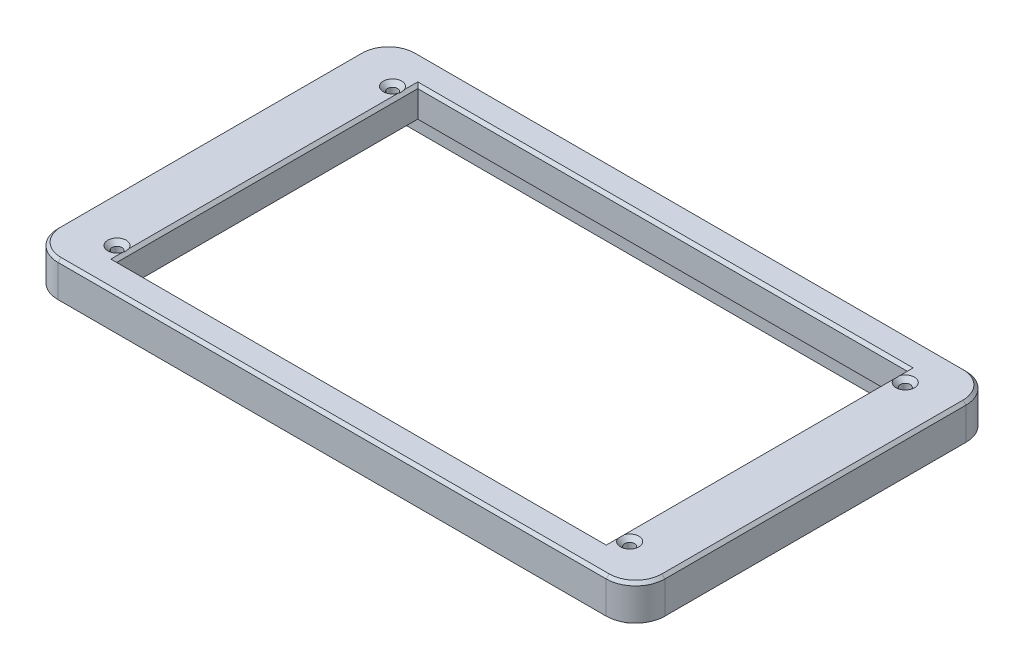
SolidWorks part; units mm, degrees
material "AÇO 1020"
ref_plane "Front Plane" through (0, 0, 0) normal (0, 0, 1) x (1, 0, 0)
ref_plane "Top Plane" through (0, 0, 0) normal (0, 1, 0) x (1, 0, 0)
ref_plane "Right Plane" through (0, 0, 0) normal (1, 0, 0) x (0, 0, -1)
sketch "Sketch1" plane through (0, 0, 0) normal (0, 1, 0) x (1, 0, 0)
  line L1 (83.5, 51.35) -> (-83.5, 51.35)
  line L2 (83.5, 51.35) -> (83.5, -51.35)
  line L3 (83.5, -51.35) -> (-83.5, -51.35)
  line L4 (-83.5, 51.35) -> (-83.5, -51.35)
  line L5 (0, -51.35) -> (0, 51.35) construction
  line L6 (83.5, 0) -> (-83.5, 0) construction
  line L7 (103.5, 61.35) -> (-103.5, 61.35)
  line L8 (103.5, 61.35) -> (103.5, -61.35)
  line L9 (103.5, -61.35) -> (-103.5, -61.35)
  line L10 (-103.5, 61.35) -> (-103.5, -61.35)
  line L11 (0, -61.35) -> (0, 61.35) construction
  line L12 (103.5, 0) -> (-103.5, 0) construction
  point P0 (0, 0)
  point P4 (0, 0)
  dimension "D1" = 102.7
  dimension "D2" = 167
  dimension "D3" = 10
  dimension "D4" = 20
extrude "Extrude1" add sketch "Sketch1" along normal blind 12
fillet "Fillet1" radius 10 4 edges at (103.5, 6, 61.35) (103.5, 6, -61.35) (-103.5, 6, -61.35) (-103.5, 6, 61.35)
chamfer "Chamfer1" distance 1 angle 45 12 edges at (0, 12, 51.35) (83.5, 12, 0) (0, 12, -51.35) (-83.5, 12, 0) (0, 12, -61.35) (103.5, 12, 0) (0, 12, 61.35) (-103.5, 12, 0) (-100.5711, 12, 58.4211) (-100.5711, 12, -58.4211) (100.5711, 12, -58.4211) (100.5711, 12, 58.4211)
sketch "Sketch2" plane through (0, 0, 0) normal (0, -1, 0) x (1, 0, 0)
  line L1 (93.45, 53) -> (-93.45, 53)
  line L2 (93.45, 53) -> (93.45, -53)
  line L3 (93.45, -53) -> (-93.45, -53)
  line L4 (-93.45, 53) -> (-93.45, -53)
  line L5 (0, -53) -> (0, 53) construction
  line L6 (93.45, 0) -> (-93.45, 0) construction
  point P0 (0, 0)
  dimension "D1" = 106
  dimension "D2" = 186.9
extrude "Extrude2" cut sketch "Sketch2" against normal blind 2
fillet "Fillet2" radius 2.5 4 edges at (-93.45, 1, -53) (93.45, 1, -53) (93.45, 1, 53) (-93.45, 1, 53)
sketch "Sketch3" plane through (0, 0, 0) normal (0, -1, 0) x (1, 0, 0)
  line L1 (97.5, 56.35) -> (-97.5, 56.35)
  line L2 (97.5, 56.35) -> (97.5, -56.35)
  line L3 (97.5, -56.35) -> (-97.5, -56.35)
  line L4 (-97.5, 56.35) -> (-97.5, -56.35)
  line L5 (0, -56.35) -> (0, 56.35) construction
  line L6 (97.5, 0) -> (-97.5, 0) construction
  line L8 (-90.95, -53) -> (90.95, -53) construction
  line L9 (93.45, -50.5) -> (93.45, 50.5) construction
  line L10 (90.95, 53) -> (-90.95, 53) construction
  line L11 (-93.45, 50.5) -> (-93.45, -50.5) construction
  line L12 (-90.95, -53) -> (90.95, -53)
  line L13 (93.45, -50.5) -> (93.45, 50.5)
  line L14 (90.95, 53) -> (-90.95, 53)
  line L15 (-93.45, 50.5) -> (-93.45, -50.5)
  arc A0 (-93.45, -50.5) -> (-90.95, -53) centre (-90.95, -50.5) ccw construction
  arc A1 (90.95, -53) -> (93.45, -50.5) centre (90.95, -50.5) ccw construction
  arc A2 (93.45, 50.5) -> (90.95, 53) centre (90.95, 50.5) ccw construction
  arc A3 (-90.95, 53) -> (-93.45, 50.5) centre (-90.95, 50.5) ccw construction
  arc A4 (-93.45, -50.5) -> (-90.95, -53) centre (-90.95, -50.5) ccw
  arc A5 (90.95, -53) -> (93.45, -50.5) centre (90.95, -50.5) ccw
  arc A6 (93.45, 50.5) -> (90.95, 53) centre (90.95, 50.5) ccw
  arc A7 (-90.95, 53) -> (-93.45, 50.5) centre (-90.95, 50.5) ccw
  point P0 (0, 0)
  dimension "D1" = 195
  dimension "D2" = 112.7
extrude "Extrude3" add sketch "Sketch3" along normal blind 3.5
hole_wizard "Ø2.0 (2) Diameter Hole1" positions "Sketch8" profile "Sketch9" hole size "Ø2.0" standard "DIN" end condition through all
sketch "Sketch8" plane through (-103.5, 2, 61.35) normal (0, -1, 0) x (1, 0, 0)
  point P0 (190.95, -14.05)
  point P3 (190.95, -108.05)
  point P6 (16.05, -108.05)
  point P9 (16.05, -14.05)
sketch "Sketch9" plane through (87.45, 2, 47.3) normal (1, 0, 0) x (0, 0, -1)
  line L0 (0, 0) -> (0, 10)
  line L1 (0, 10) -> (1, 10)
  line L2 (1, 10) -> (1, 0)
  line L3 (1, 0) -> (0, 0)
  line L4 (0, -6.35) -> (0, 107.95) construction
  dimension "Thru Hole Dia." = 2
  dimension "Thru Hole Depth" = 10
hole_wizard "CSK for M3 Countersunk Raised Head Screw2" positions "Sketch10" profile "Sketch11" countersink size "M3" standard "DIN" end condition through all
sketch "Sketch10" plane through (0, 12, 0) normal (0, 1, 0) x (1, 0, 0)
  point P0 (87.45, 46.7)
  point P3 (87.45, -47.3)
  point P6 (-87.45, -47.3)
  point P9 (-87.45, 46.7)
sketch "Sketch11" plane through (87.45, 12, -46.7) normal (1, 0, 0) x (0, 0, 1)
  line L0 (0, 0) -> (0, 15.5)
  line L1 (0, 15.5) -> (1.7, 15.5)
  line L2 (1.7, 15.5) -> (1.7, 1.45)
  line L3 (1.7, 1.45) -> (3.15, 0)
  line L5 (3.15, 0) -> (0, 0)
  line L6 (-1.7, 1.45) -> (-3.15, 0) construction
  line L11 (0, -6.35) -> (0, 107.95) construction
  dimension "Thru Hole Dia." = 3.4
  dimension "Thru Hole Depth" = 15.5
  dimension "Near C'Sink Dia." = 6.3
  dimension "Near C'Sink Angle" = 90
chamfer "Chamfer2" distance 2 angle 45 4 edges at (-97.5, -1.75, 56.35) (-97.5, -1.75, -56.35) (97.5, -1.75, -56.35) (97.5, -1.75, 56.35)
sketch "Sketch12" plane through (-97.5, 0, 0) normal (-1, 0, 0) x (0, 0, 1)
  line L0 (-51.35, 0) -> (51.35, 0) construction
  line L1 (-15, -1.5) -> (15, -1.5)
  line L2 (-15, -1.5) -> (-15, -3.5)
  line L3 (-15, -3.5) -> (15, -3.5)
  line L4 (15, -1.5) -> (15, -3.5)
  line L5 (0, -3.5) -> (0, -1.5) construction
  line L6 (-15, -2.5) -> (15, -2.5) construction
  point P0 (0, -2.5)
  dimension "D1" = 2
  dimension "D2" = 1.5
  dimension "D3" = 30
extrude "Extrude4" add sketch "Sketch12" along normal blind 1.5
fillet "Fillet3" radius 1 2 edges at (-99, -3.5, 0) (-99, -1.5, 0)
ref_plane "Plane1" through (0, 0, 0) normal (-1, 0, 0) x (0, 0, 1)
sketch "Sketch13" plane through (97.5, 0, 0) normal (1, 0, 0) x (0, 0, -1)
  line L0 (-51.35, 0) -> (51.35, 0) construction
  line L1 (-15, -1.5) -> (15, -1.5)
  line L2 (-15, -1.5) -> (-15, -3.5)
  line L3 (-15, -3.5) -> (15, -3.5)
  line L4 (15, -1.5) -> (15, -3.5)
  line L5 (0, -3.5) -> (0, -1.5) construction
  line L6 (-15, -2.5) -> (15, -2.5) construction
  line L7 (54.35, -3.5) -> (-54.35, -3.5) construction
  point P0 (0, -2.5)
  dimension "D1" = 30
  dimension "D2" = 1.5
extrude "Extrude5" add sketch "Sketch13" along normal blind 1.5
fillet "Fillet4" radius 1 2 edges at (99, -1.5, 0) (99, -3.5, 0)
sketch "Sketch14" plane through (0, 0, 56.35) normal (0, 0, 1) x (1, 0, 0)
  line L0 (95.5, -3.5) -> (-95.5, -3.5) construction
  line L1 (-15, -1.5) -> (15, -1.5)
  line L2 (-15, -1.5) -> (-15, -3.5)
  line L3 (-15, -3.5) -> (15, -3.5)
  line L4 (15, -1.5) -> (15, -3.5)
  line L5 (0, -3.5) -> (0, -1.5) construction
  line L6 (-15, -2.5) -> (15, -2.5) construction
  line L7 (95.5, 0) -> (-95.5, 0) construction
  point P0 (0, -2.5)
  dimension "D1" = 1.5
  dimension "D2" = 30
extrude "Extrude6" add sketch "Sketch14" along normal blind 1.5
fillet "Fillet5" radius 1 2 edges at (0, -3.5, 57.85) (0, -1.5, 57.85)
sketch "Sketch15" plane through (0, 0, -56.35) normal (0, 0, -1) x (-1, 0, 0)
  line L0 (-93.5, 0) -> (93.5, 0) construction
  line L1 (-15, -1.5) -> (15, -1.5)
  line L2 (-15, -1.5) -> (-15, -3.5)
  line L3 (-15, -3.5) -> (15, -3.5)
  line L4 (15, -1.5) -> (15, -3.5)
  line L5 (0, -3.5) -> (0, -1.5) construction
  line L6 (-15, -2.5) -> (15, -2.5) construction
  line L7 (95.5, -3.5) -> (-95.5, -3.5) construction
  point P0 (0, -2.5)
  dimension "D1" = 1.5
  dimension "D2" = 30
extrude "Extrude7" add sketch "Sketch15" along normal blind 1.5
fillet "Fillet6" radius 1 2 edges at (0, -3.5, -57.85) (0, -1.5, -57.85)
